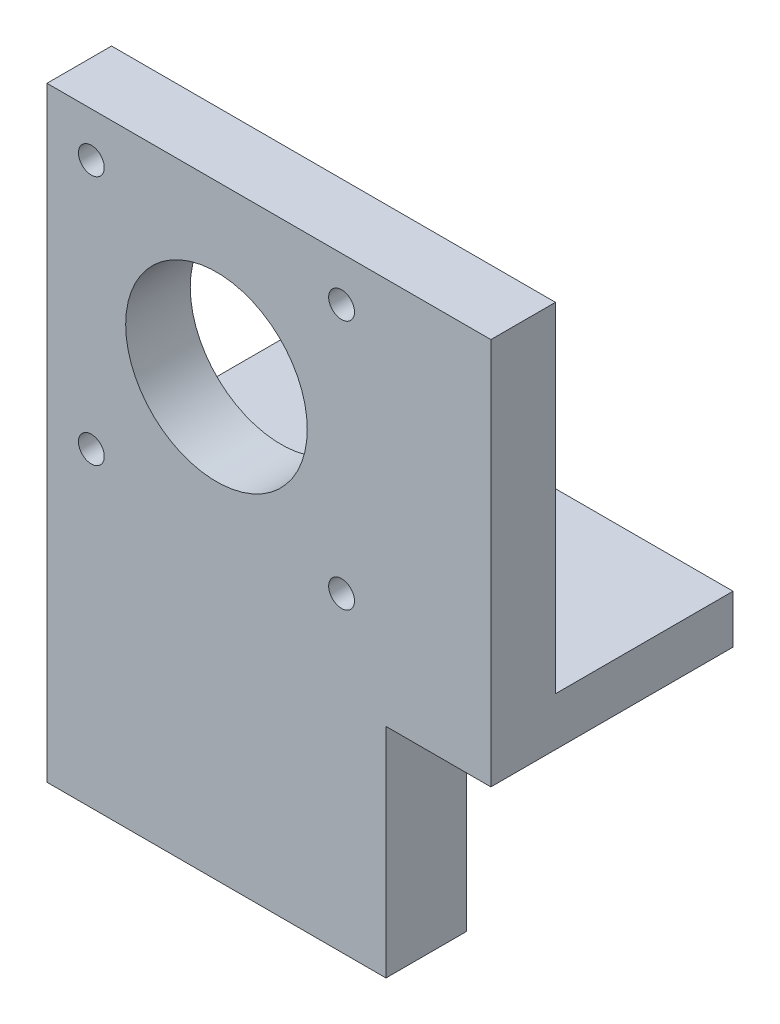
SolidWorks part; units mm, degrees
ref_plane "Front Plane" through (0, 0, 0) normal (0, 0, 1) x (1, 0, 0)
ref_plane "Top Plane" through (0, 0, 0) normal (0, 1, 0) x (1, 0, 0)
ref_plane "Right Plane" through (0, 0, 0) normal (1, 0, 0) x (0, 0, -1)
sketch "Sketch1" plane through (0, 0, 0) normal (0, 1, 0) x (1, 0, 0)
  line L1 (-8, 7.5) -> (8, 7.5) construction
  line L2 (-8, 7.5) -> (-8, -7.5) construction
  line L3 (-8, -7.5) -> (8, -7.5) construction
  line L4 (8, 7.5) -> (8, -7.5) construction
  line L5 (-8, 7.5) -> (8, -7.5) construction
  line L6 (-8, -7.5) -> (8, 7.5) construction
  line L7 (-21, 10) -> (21, 10) construction
  line L8 (-21, 10) -> (-21, -10) construction
  line L9 (-21, -10) -> (21, -10) construction
  line L10 (21, 10) -> (21, -10) construction
  line L11 (-21, 10) -> (21, -10) construction
  line L12 (-21, -10) -> (21, 10) construction
  line L13 (-21, -10) -> (21, -10) construction
  line L14 (-21, -10) -> (-21, -20) construction
  line L15 (-21, -20) -> (21, -20) construction
  line L16 (21, -10) -> (21, -20) construction
  point P0 (0, 0)
  point P1 (8, -7.5)
  point P2 (-8, 7.5)
  point P3 (-8, -7.5)
  point P4 (8, 7.5)
  point P6 (0, 0)
  point P18 (-8, 7.5)
  dimension "D1" = 16
  dimension "D2" = 15
  dimension "D3" = 20
  dimension "D4" = 42
  dimension "D5" = 10
sketch "Sketch3" plane through (0, 0, 0) normal (0, 1, 0) x (1, 0, 0)
  line L1 (-21, 10) -> (21, 10)
  line L2 (-21, 10) -> (-21, -20)
  line L3 (-21, -20) -> (21, -20)
  line L4 (21, 10) -> (21, -20)
extrude "Boss-Extrude1" add sketch "Sketch3" against normal blind 8
sketch "Sketch4" plane through (0, -8, 0) normal (0, -1, 0) x (1, 0, 0)
  line L1 (-21, 20) -> (21, 20)
  line L2 (-21, 20) -> (-21, 10)
  line L3 (-21, 10) -> (21, 10)
  line L4 (21, 20) -> (21, 10)
extrude "Boss-Extrude2" add sketch "Sketch4" along normal blind 25
sketch "Sketch8" plane through (0, 0, 0) normal (0, 1, 0) x (1, 0, 0)
  point P0 (8, -7.5)
  point P2 (-8, -7.5)
  point P4 (8, 7.5)
  point P6 (-8, 7.5)
hole_wizard "CSK for M3 Flat Head Machine Screw1" positions "Sketch8" profile "Sketch9" countersink size "M3" standard "ANSI Metric" end condition through all
sketch "Sketch9" plane through (8, 0, 7.5) normal (1, 0, 0) x (0, 0, 1)
  line L0 (0, 0) -> (0, 33)
  line L1 (0, 33) -> (1.6, 33)
  line L2 (1.6, 33) -> (1.6, 1.55)
  line L3 (1.6, 1.55) -> (3.15, 0)
  line L5 (3.15, 0) -> (0, 0)
  line L6 (-1.6, 1.55) -> (-3.15, 0) construction
  line L11 (0, -6.35) -> (0, 107.95) construction
  dimension "Thru Hole Dia." = 3.2
  dimension "Thru Hole Depth" = 33
  dimension "Near C'Sink Dia." = 6.3
  dimension "Near C'Sink Angle" = 90
sketch "Sketch10" plane through (0, 0, 0) normal (0, 1, 0) x (1, 0, 0)
  line L0 (-21, -10) -> (-21, -20) construction
  line L1 (-21, -12) -> (21, -12)
  line L2 (-21, -12) -> (-21, -20)
  line L3 (-21, -20) -> (21, -20)
  line L4 (21, -12) -> (21, -20)
  line L5 (21, -10) -> (21, -20) construction
  line L6 (-21, -10) -> (21, -10) construction
  dimension "D1" = 2
  dimension "D2" = 8
extrude "Boss-Extrude3" add sketch "Sketch10" along normal blind 42
sketch "Sketch11" plane through (0, 0, 12) normal (0, 0, -1) x (-1, 0, 0)
  line L1 (-15.5, 36.5) -> (15.5, 36.5) construction
  line L2 (-15.5, 36.5) -> (-15.5, 5.5) construction
  line L3 (-15.5, 5.5) -> (15.5, 5.5) construction
  line L4 (15.5, 36.5) -> (15.5, 5.5) construction
  line L5 (21, 42) -> (21, 0) construction
  line L6 (-21, 42) -> (21, 42) construction
  circle A0 centre (0, 21) radius 11.25
  dimension "D5" = 22.5
  dimension "D1" = 5.5
  dimension "D2" = 5.5
  dimension "D3" = 31
  dimension "D4" = 31
extrude "Cut-Extrude1" cut sketch "Sketch11" against normal blind 42
sketch "Sketch12" plane through (0, 0, 12) normal (0, 0, -1) x (-1, 0, 0)
  point P0 (15.5, 5.5)
  point P2 (-15.5, 5.5)
  point P4 (15.5, 36.5)
  point P6 (-15.5, 36.5)
hole_wizard "M3 Clearance Hole4" positions "Sketch12" profile "Sketch13" hole size "M3" standard "ANSI Metric" end condition through all
sketch "Sketch13" plane through (-15.5, 5.5, 12) normal (1, 0, 0) x (0, 1, 0)
  line L0 (0, 0) -> (0, 8)
  line L1 (0, 8) -> (1.6, 8)
  line L2 (1.6, 8) -> (1.6, 0)
  line L5 (1.6, 0) -> (0, 0)
  line L11 (0, -6.35) -> (0, 107.95) construction
  dimension "Thru Hole Dia." = 3.2
  dimension "Thru Hole Depth" = 8
sketch "Sketch14" plane through (21, 0, 0) normal (1, 0, 0) x (0, 0, -1)
  line L0 (10, 0) -> (-10, 0) construction
  line L1 (10, 0) -> (-10, 0)
  line L2 (10, 0) -> (10, -6)
  line L3 (10, -6) -> (-10, -6)
  line L5 (10, 0) -> (-10, 0) construction
  line L6 (-10, 0) -> (-12, 0)
  line L7 (-20, 42) -> (-12, 42)
  line L8 (-20, 42) -> (-20, -6)
  line L9 (-20, -6) -> (-12, -6)
  line L10 (-12, 42) -> (-12, 0)
  line L11 (-10, 0) -> (-20, 0) construction
  line L12 (-10, -6) -> (-12, -6)
  dimension "D1" = 6
  dimension "D2" = 20
extrude "Boss-Extrude4" add sketch "Sketch14" along normal blind 13
sketch "Sketch15" plane through (-21, 0, 0) normal (-1, 0, 0) x (0, 0, 1)
  line L8 (12, 0) -> (-10, 0)
  line L9 (-10, 0) -> (-10, -8)
  line L10 (-10, -8) -> (10, -8)
  line L11 (10, -8) -> (10, -33)
  line L12 (10, -33) -> (20, -33)
  line L13 (20, -33) -> (20, 42)
  line L14 (20, 42) -> (12, 42)
  line L15 (12, 42) -> (12, 0)
  line L16 (12, 0) -> (-10, 0)
  line L17 (-10, 0) -> (-10, -8)
  line L18 (-10, -8) -> (10, -8)
  line L19 (10, -8) -> (10, -33)
  line L20 (10, -33) -> (20, -33)
  line L21 (20, -33) -> (20, 42)
  line L22 (20, 42) -> (12, 42)
  line L23 (12, 42) -> (12, 0)
  dimension "D1" = 0
chamfer "Chamfer2" distance 2 angle 45 1 edges at (-21, -8, 0)
